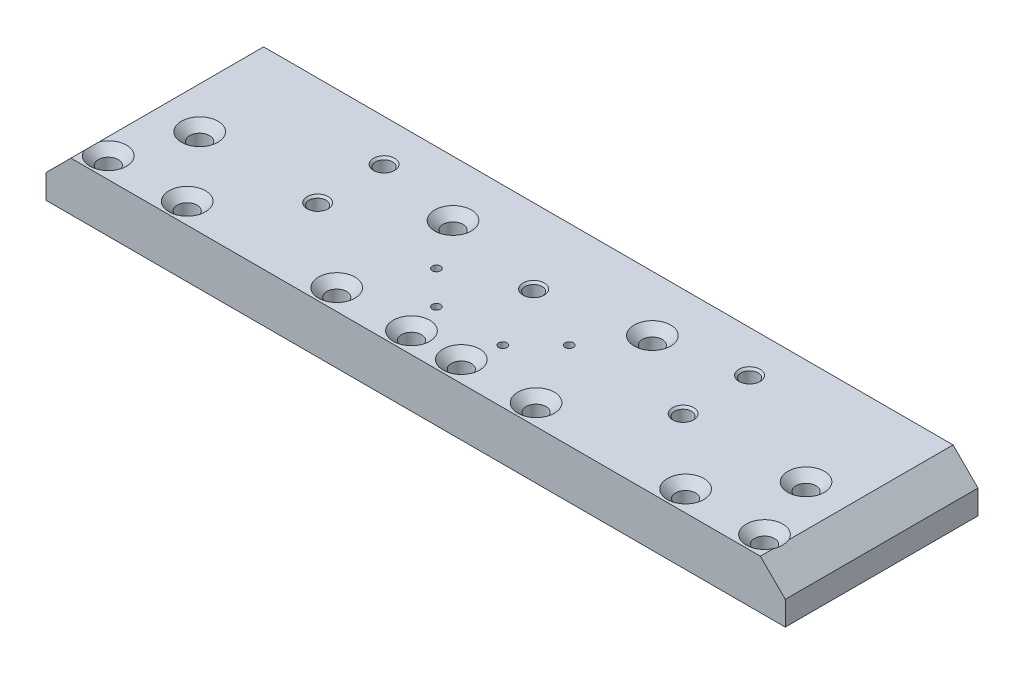
SolidWorks part; units mm, degrees
material "6061-T6 (SS)"
ref_plane "Front Plane" through (0, 0, 0) normal (0, 0, 1) x (1, 0, 0)
ref_plane "Top Plane" through (0, 0, 0) normal (0, 1, 0) x (1, 0, 0)
ref_plane "Right Plane" through (0, 0, 0) normal (1, 0, 0) x (0, 0, -1)
sketch "Sketch1" plane through (0, 0, 0) normal (0, 1, 0) x (1, 0, 0)
  line L1 (44.5, -11.6) -> (-44.5, -11.6)
  line L2 (44.5, -11.6) -> (44.5, 11.6)
  line L3 (44.5, 11.6) -> (-44.5, 11.6)
  line L4 (-44.5, -11.6) -> (-44.5, 11.6)
  line L5 (44.5, -11.6) -> (-44.5, 11.6) construction
  line L6 (44.5, 11.6) -> (-44.5, -11.6) construction
  point P0 (0, 0)
  dimension "D1" = 89
  dimension "D2" = 23.2
extrude "Boss-Extrude1" add sketch "Sketch1" along normal blind 4 and the other way blind 1.9
hole_wizard "M2.5x0.45 Tapped Hole2" positions "Sketch4" profile "Sketch5" tap size "M2.5x0.45" standard "ANSI Metric" end condition through all
sketch "Sketch4" plane through (0, 4, 0) normal (0, 1, 0) x (1, 0, 0)
  line L0 (44.5, 11.6) -> (-44.5, 11.6) construction
  point P0 (-22, 6.6)
  point P2 (-22, -1.4)
  point P4 (22, -1.4)
  point P6 (22, 6.6)
  point P8 (0, 2.6)
  dimension "D1" = 8
  dimension "D2" = 8
  dimension "D3" = 44
  dimension "D4" = 22
  dimension "D5" = 9
  dimension "D6" = 4
  dimension "D7" = 4
cosmetic thread "Hole Thread6" parameters "D2"=2.5
cosmetic thread "Hole Thread7" parameters "D2"=2.5
cosmetic thread "Hole Thread8" parameters "D2"=2.5
cosmetic thread "Hole Thread9" parameters "D2"=2.5
cosmetic thread "Hole Thread10" parameters "D2"=2.5
sketch "Sketch5" plane through (-22, 4, -6.6) normal (1, 0, 0) x (0, 0, 1)
  line L0 (0, 0) -> (0, 5.9)
  line L1 (0, 5.9) -> (1.025, 5.9)
  line L2 (1.025, 5.9) -> (1.025, 0.25)
  line L3 (1.025, 0.25) -> (1.275, 0)
  line L5 (1.275, 0) -> (0, 0)
  line L6 (-1.025, 0.25) -> (-1.275, 0) construction
  line L11 (0, -6.35) -> (0, 107.95) construction
  dimension "Thru Tap Drill Dia." = 2.05
  dimension "Thru Tap Drill Depth" = 5.9
  dimension "Near C'Sink Dia." = 2.55
  dimension "Near C'Sink Angle" = 90
hole_wizard "CSK for M2 Flat Head Machine Screw1" positions "Sketch6" profile "Sketch7" countersink size "M2" standard "ANSI Metric"
sketch "Sketch6" plane through (0, 4, 0) normal (0, 1, 0) x (1, 0, 0)
  line L0 (-44.5, -11.6) -> (44.5, -11.6) construction
  line L1 (-39.5, -9.1) -> (-30, -9.1) construction
  line L2 (-30, -9.1) -> (30, -9.1) construction
  line L3 (30, -9.1) -> (39.5, -9.1) construction
  line L5 (0, 0) -> (0, -11.6) construction
  line L7 (-12, -9.1) -> (-12, 4.9) construction
  circle A0 centre (0, 2.6) radius 1.025 construction
  point P0 (-36.5, -1.1)
  point P2 (-39.5, -9.1)
  point P4 (-30, -9.1)
  point P6 (30, -9.1)
  point P8 (39.5, -9.1)
  point P10 (36.5, -1.1)
  point P41 (-3, -9.1)
  point P43 (-12, -9.1)
  point P47 (12, -9.1)
  point P48 (3, -9.1)
  point P64 (-12, 4.9)
  point P66 (12, 4.9)
  point P67 (-12, -9.1)
  dimension "D5" = 39.5
  dimension "D1" = 39.5
  dimension "D2" = 3
  dimension "D3" = 8
  dimension "D4" = 9.5
  dimension "D6" = 3
  dimension "D7" = 9.5
  dimension "D8" = 8
  dimension "D9" = 2.5
  dimension "D10" = 2.5
  dimension "D11" = 9
  dimension "D12" = 6
  dimension "D14" = 14
sketch "Sketch7" plane through (-36.5, 4, 1.1) normal (1, 0, 0) x (0, 0, 1)
  line L0 (0, 0) -> (0, 7.171)
  line L1 (0, 7.171) -> (1.2, 6.45)
  line L2 (1.2, 6.45) -> (1.2, 1)
  line L3 (1.2, 1) -> (2.2, 0)
  line L5 (2.2, 0) -> (0, 0)
  line L6 (-1.2, 1) -> (-2.2, 0) construction
  line L10 (0, 7.171) -> (-1.2, 6.45) construction
  line L11 (0, -6.35) -> (0, 107.95) construction
  dimension "Hole Dia." = 2.4
  dimension "Hole Depth" = 6.45
  dimension "Near C'Sink Dia." = 4.4
  dimension "Near C'Sink Angle" = 90
  dimension "Drill Angle" = 118
sketch "Sketch8" plane through (0, 0, 11.6) normal (0, 0, 1) x (1, 0, 0)
  line L9 (41.5, 4) -> (44.5, 4)
  line L10 (-44.5, 4) -> (44.5, 4) construction
  line L11 (44.5, 4) -> (44.5, 1)
  line L12 (44.5, 4) -> (44.5, -1.9) construction
  line L13 (44.5, 1) -> (41.5, 4)
  line L14 (-44.5, 4) -> (-44.5, 1)
  line L15 (-44.5, 4) -> (-44.5, -1.9) construction
  line L16 (-44.5, 1) -> (-41.5, 4)
  line L17 (-41.5, 4) -> (-44.5, 4)
  dimension "D1" = 3
  dimension "D2" = 2.9
  dimension "D3" = 2.9
  dimension "D4" = 3
extrude "Cut-Extrude1" cut sketch "Sketch8" against normal up to surface (23.2 mm away) up to face at (0, 1.05, -11.6)
hole_wizard "Ø1.0mm Dowel Hole1" positions "3DSketch1" profile "Sketch10" hole size "Ø1.0" standard "ANSI Metric" end condition through all
sketch3d "3DSketch1"
  line L0 (0, 4, 11.6) -> (0, 4, -11.6) construction
  line L1 (-41.5, 4, 11.6) -> (41.5, 4, 11.6) construction
  line L2 (41.5, 4, -11.6) -> (-41.5, 4, -11.6) construction
  line L4 (0, 4, 5.1) -> (-4, 4, 5.1) construction
  line L6 (-8, 4, 1.1) -> (0, 4, 1.1) construction
  point P0 (-8, 4, 1.1)
  point P2 (-4, 4, 5.1)
  dimension "D1" = 4
  dimension "D2" = 8
  dimension "D3" = 4
  dimension "D4" = 6.5
sketch "Sketch10" plane through (-8, 4, 1.1) normal (1, 0, 0) x (0, 0, 1)
  line L0 (0, 0) -> (0, 5.9)
  line L1 (0, 5.9) -> (0.5, 5.9)
  line L2 (0.5, 5.9) -> (0.5, 0)
  line L5 (0.5, 0) -> (0, 0)
  line L11 (0, -6.35) -> (0, 107.95) construction
  dimension "Thru Hole Dia." = 1
  dimension "Thru Hole Depth" = 5.9
hole_wizard "Ø1.5mm Dowel Hole1" positions "3DSketch2" profile "Sketch11" hole size "Ø1.5" standard "ANSI Metric"
sketch3d "3DSketch2"
  line L1 (-4, -1.9, 5.1) -> (-4, 4, 5.1) construction
  line L2 (-8, -1.9, 1.1) -> (-8, 4, 1.1) construction
  point P4 (-4, -1.9, 5.1)
  point P9 (-8, -1.9, 1.1)
sketch "Sketch11" plane through (-4, -1.9, 5.1) normal (1, 0, 0) x (0, 0, -1)
  line L0 (0, 0) -> (0, 3.4506)
  line L1 (0, 3.4506) -> (0.75, 3)
  line L2 (0.75, 3) -> (0.75, 0)
  line L5 (0.75, 0) -> (0, 0)
  line L10 (0, 3.4506) -> (-0.75, 3) construction
  line L11 (0, -6.35) -> (0, 107.95) construction
  dimension "Hole Dia." = 1.5
  dimension "Hole Depth" = 3
  dimension "Drill Angle" = 118
mirror "Mirror1" about plane through (0, 0, 0) normal (1, 0, 0) of "Ø1.5mm Dowel Hole1", "Ø1.0mm Dowel Hole1"
